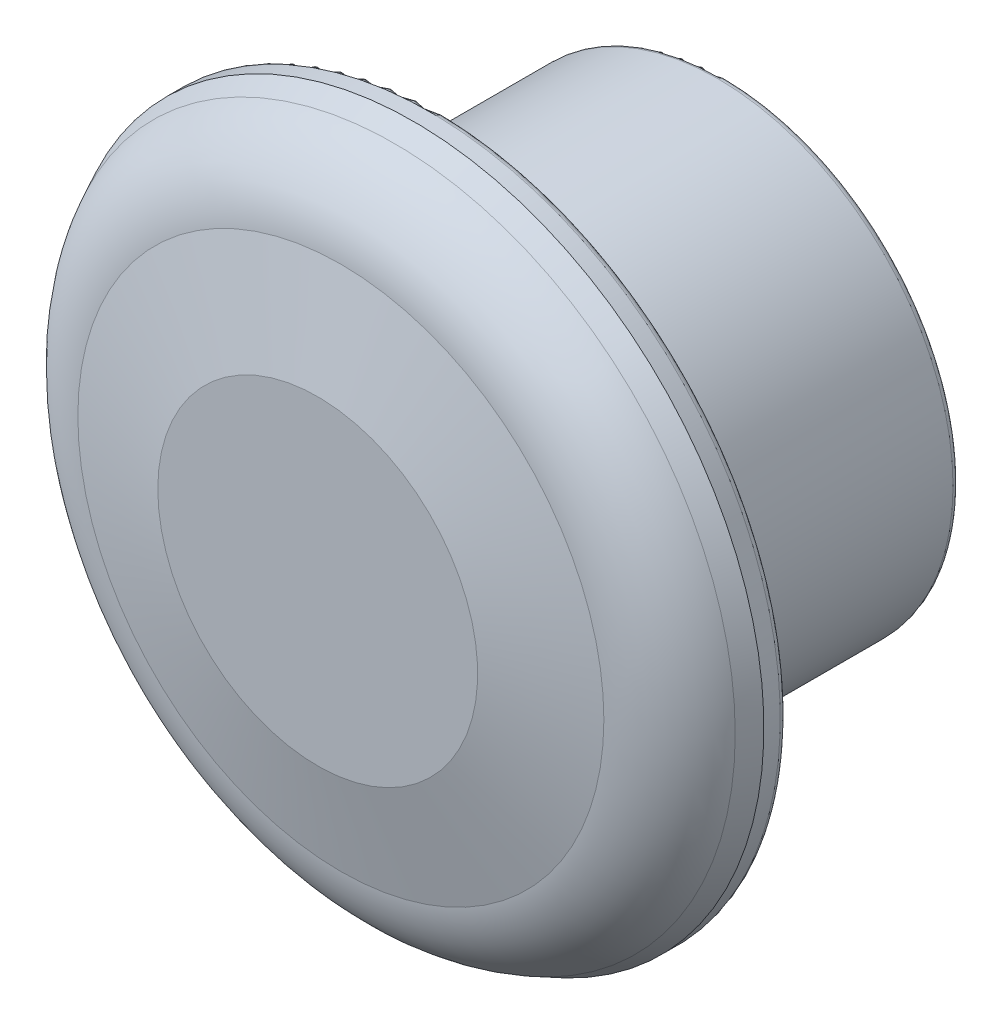
SolidWorks part; units mm, degrees
ref_plane "Front Plane" through (0, 0, 0) normal (0, 0, 1) x (1, 0, 0)
ref_plane "Top Plane" through (0, 0, 0) normal (0, 1, 0) x (1, 0, 0)
ref_plane "Right Plane" through (0, 0, 0) normal (1, 0, 0) x (0, 0, -1)
sketch "Sketch1" plane through (0, 0, 0) normal (1, 0, 0) x (0, 0, -1)
  line L0 (0, 0) -> (0, 10.95) construction
  line L1 (0, 10.95) -> (3, 10.95) construction
  line L3 (2.3972, 10.656) -> (3, 10.95)
  line L4 (3, 10.95) -> (3.7122, 10.95)
  line L5 (3.7122, 10.95) -> (3.7122, 8.9)
  line L6 (3.7122, 8.9) -> (4.7122, 8.9)
  line L7 (4.7122, 8.9) -> (4.7122, 7.35)
  line L8 (4.7122, 7.35) -> (12.7122, 7.35)
  line L11 (0, 0) -> (0, 5)
  line L12 (0, 5) -> (0.7238, 8.2226)
  line L13 (12.7122, 7.35) -> (12.7122, 6.35)
  line L14 (12.7122, 6.35) -> (3.2567, 6.35)
  line L18 (1.8825, 0) -> (0, 0)
  line L19 (3.2567, 6.35) -> (2.8825, 6.35)
  line L20 (1.8825, 5.35) -> (1.8825, 0)
  arc A0 (0.7238, 8.2226) -> (2.3972, 10.656) centre (3.7122, 7.9596) cw
  arc A1 (2.8825, 6.35) -> (1.8825, 5.35) centre (2.8825, 5.35) ccw
  point P7 (0, 0)
  point P17 (2.0216, 6.35)
  point P19 (3.2567, 6.35)
  dimension "D3" = 3
  dimension "D10" = 1
  dimension "D1" = 10.95
  dimension "D2" = 3
  dimension "D4" = 2.05
  dimension "D5" = 1
  dimension "D6" = 1.55
  dimension "D7" = 8
  dimension "D8" = 1
  dimension "D9" = 5
revolve "Revolve1" add sketch "Sketch1" angle 360 about L18
fillet "Fillet2" radius 0.2 4 edges at (-6.35, 0, -12.7122) (-10.95, 0, -3.7122) (-8.9, 0, -4.7122) (-7.35, 0, -12.7122)
